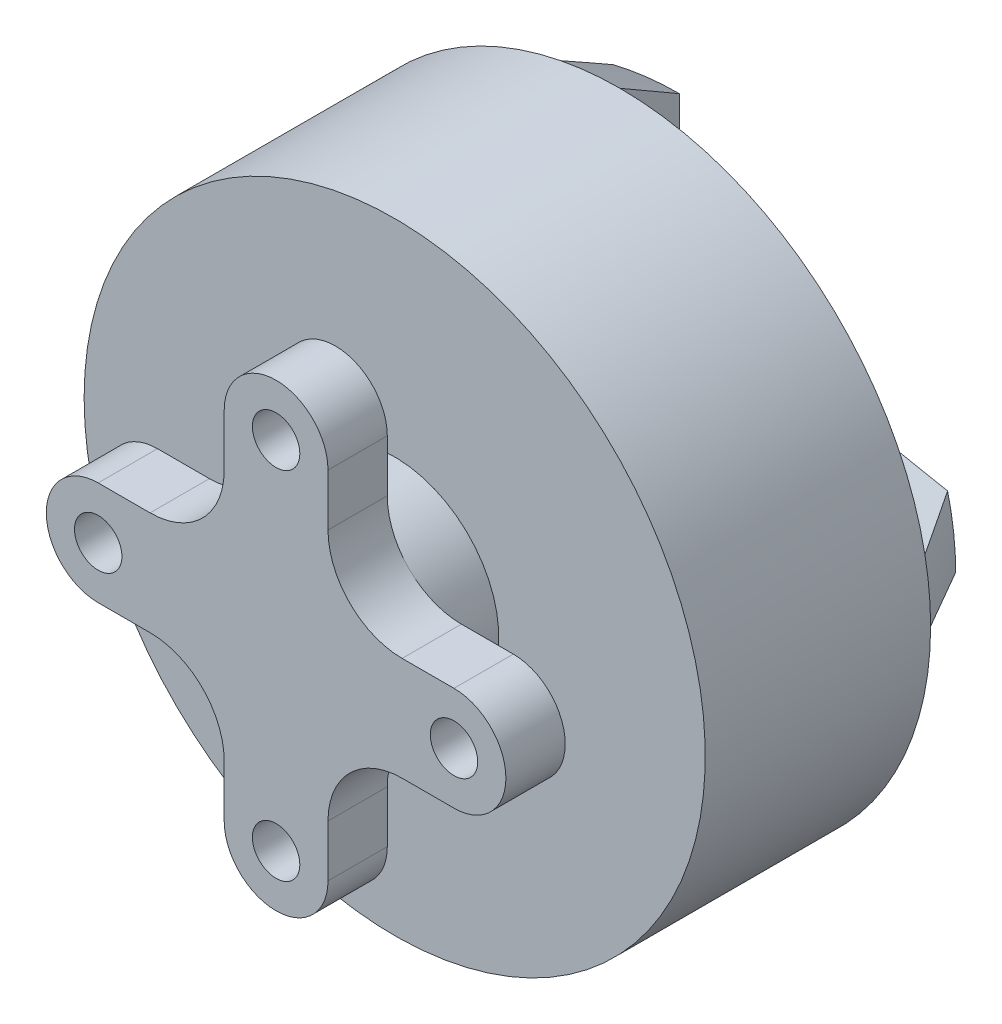
SolidWorks part; units mm, degrees
ref_plane "Front Plane" through (0, 0, 0) normal (1, 0, 0) x (0, 1, 0)
ref_plane "Top Plane" through (0, 0, 0) normal (0, 0, 1) x (0, 1, 0)
ref_plane "Right Plane" through (0, 0, 0) normal (0, 1, 0) x (-1, 0, 0)
sketch "Sketch1" plane through (0, 0, 0) normal (0, 0, 1) x (0, 1, 0)
  line L0 (-1.75, 1.75) -> (-1.75, 6)
  line L2 (1.75, 6) -> (1.75, 1.75)
  line L13 (0, 0) -> (1.5513, 0) construction
  line L16 (0, 0) -> (0, 1.4954) construction
  line L17 (1.75, 1.75) -> (6, 1.75)
  line L18 (6, -1.75) -> (1.75, -1.75)
  line L19 (1.75, -1.75) -> (1.75, -6)
  line L20 (-1.75, -6) -> (-1.75, -1.75)
  line L21 (-1.75, -1.75) -> (-6, -1.75)
  line L22 (-6, 1.75) -> (-1.75, 1.75)
  circle A2 centre (0, 6) radius 0.8
  arc A4 (1.75, 6) -> (-1.75, 6) centre (0, 6) ccw
  circle A5 centre (6, 0) radius 0.8
  arc A6 (6, -1.75) -> (6, 1.75) centre (6, 0) ccw
  circle A7 centre (0, -6) radius 0.8
  arc A8 (-1.75, -6) -> (1.75, -6) centre (0, -6) ccw
  circle A9 centre (-6, 0) radius 0.8
  arc A10 (-6, 1.75) -> (-6, -1.75) centre (-6, 0) ccw
  point P1 (-1.75, 1.8442)
  point P10 (5.2, 0)
  point P21 (0, -5.2)
  point P26 (0, 5.2)
  point P29 (-5.2, 0)
  point P35 (0, 0)
  dimension "D2" = 1.6
  dimension "D3" = 1.75
  dimension "D1" = 10.4
  dimension "D4" = 4
extrude "Boss-Extrude1" add sketch "Sketch1" along normal blind 2
fillet "Fillet2" radius 2.5 4 edges at (1.75, 1.75, 1) (1.75, -1.75, 1) (-1.75, -1.75, 1) (-1.75, 1.75, 1)
sketch "Sketch2" plane through (0, 0, 0) normal (0, 0, -1) x (1, 0, 0)
  circle A0 centre (0, 0) radius 3.5104
  arc A2 (1.75, 4.25) -> (4.25, 1.75) centre (4.25, 4.25) ccw construction
extrude "Boss-Extrude2" add sketch "Sketch2" along normal blind 2
sketch "Sketch3" plane through (0, 0, 0) normal (0, 0, 1) x (0, 1, 0)
  circle A0 centre (0, 0) radius 10.475
  dimension "D1" = 20.95
extrude "Boss-Extrude3" add sketch "Sketch3" against normal blind 7.6 from surface starting at face at (-3.5104, 0, -2)
sketch "Sketch4" plane through (0, 0, -9.6) normal (0, 0, -1) x (1, 0, 0)
  circle A0 centre (0, 0) radius 8.475
  circle A1 centre (0, 0) radius 10.475 construction
  dimension "D1" = 2
extrude "Cut-Extrude1" cut sketch "Sketch4" against normal blind 2
sketch "Sketch5" plane through (0, 0, -9.6) normal (0, 0, -1) x (1, 0, 0)
  line L0 (0, 0) -> (-4, 0)
  line L1 (-4, 0) -> (-2, -10.2823)
  line L2 (0, 0) -> (0, -10.475)
  line L3 (-1.7, -1.7) -> (-1.7, 0) construction
  line L4 (-1.7, -1.7) -> (0, -1.7) construction
  line L5 (-1.7, 1.7) -> (-1.412, 1.7) construction
  line L6 (-1.7, 1.7) -> (-1.7, 1.535) construction
  line L7 (-1.7, -0.95) -> (-1.7, 0) construction
  line L8 (-1.7, 0.95) -> (-1.7, 0) construction
  circle A0 centre (0, 0) radius 10.475 construction
  circle A2 centre (-1.7, -1.7) radius 0.75
  circle A3 centre (-1.7, 1.7) radius 0.75 construction
  circle A7 centre (0, 0) radius 10.475
  arc A8 (-2, -10.2823) -> (0, -10.475) centre (0, 0) ccw
  point P12 (-1.7, -0.95)
  point P13 (-1.7, 0.95)
  point P18 (0, -10.4744)
  point P27 (0, 0)
  dimension "D1" = 1.5
  dimension "D2" = 1.9
  dimension "D3" = 2
  dimension "D4" = 4
  dimension "D6" = 0
extrude "Boss-Extrude4" add sketch "Sketch5" along normal blind 2
chamfer "Chamfer1" distance 2 angle 30 1 edges at (-1.0046, 10.4267, -11.6) first distance on face at (-0.5, 5.1893, -10.6)
pattern_circular "CirPattern2" count 4 over 360 about axis through (0, 0, -7.6) along (0, 0, -1) of "Chamfer1", "Boss-Extrude4"
sketch "Sketch6" plane through (0, 0, -11.6) normal (0, 0, -1) x (1, 0, 0)
  circle A0 centre (0, 0) radius 0.73
  dimension "D1" = 1.46
extrude "Boss-Extrude5" add sketch "Sketch6" along normal blind 3.5
